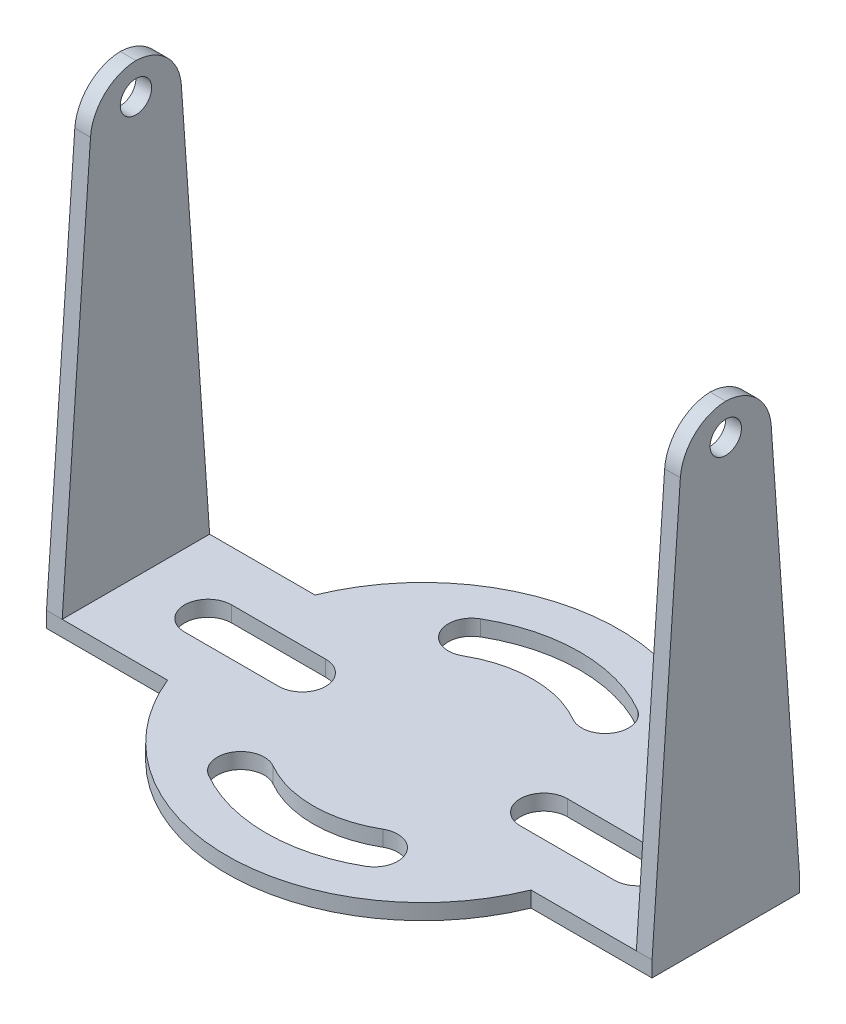
SolidWorks part; units mm, degrees
ref_plane "前视基准面" through (0, 0, 0) normal (0, 0, 1) x (1, 0, 0)
ref_plane "上视基准面" through (0, 0, 0) normal (0, 1, 0) x (1, 0, 0)
ref_plane "右视基准面" through (0, 0, 0) normal (1, 0, 0) x (0, 0, -1)
sketch "草图2" plane through (0, 0, 0) normal (0, 1, 0) x (1, 0, 0)
  line L1 (19.3, -4.7) -> (-19.3, -4.7)
  line L2 (19.3, -4.7) -> (19.3, 4.7)
  line L3 (19.3, 4.7) -> (-19.3, 4.7)
  line L4 (-19.3, -4.7) -> (-19.3, 4.7)
  line L5 (19.3, -4.7) -> (-19.3, 4.7) construction
  line L6 (19.3, 4.7) -> (-19.3, -4.7) construction
  point P0 (0, 0)
  dimension "D1" = 38.6
  dimension "D2" = 9.4
extrude "凸台-拉伸1" add sketch "草图2" along normal blind 1
sketch "草图3" plane through (0, 1, 0) normal (0, 1, 0) x (1, 0, 0)
  line L0 (-19.3, -4.7) -> (19.3, -4.7) construction
  line L1 (-19.3, 4.7) -> (-18.3, 4.7)
  line L2 (-19.3, 4.7) -> (-19.3, -4.7)
  line L3 (-19.3, -4.7) -> (-18.3, -4.7)
  line L4 (-18.3, 4.7) -> (-18.3, -4.7)
  line L5 (0, 0) -> (0, 4.7) construction
  line L6 (19.3, 4.7) -> (18.3, 4.7)
  line L7 (19.3, 4.7) -> (19.3, -4.7)
  line L8 (19.3, -4.7) -> (18.3, -4.7)
  line L9 (18.3, 4.7) -> (18.3, -4.7)
  line L10 (19.3, 4.7) -> (-19.3, 4.7) construction
  dimension "D1" = 1
extrude "凸台-拉伸2" add sketch "草图3" along normal blind 28.5
sketch "草图4" plane through (0, 1, 0) normal (0, 1, 0) x (1, 0, 0)
  line L0 (0, 0) -> (7, 0) construction
  line L4 (0, 0) -> (4.25, 7.3612)
  line L5 (0, 8.5) -> (0, 0) construction
  circle A0 centre (0, 0) radius 12.5
  circle A1 centre (0, 0) radius 7 construction
  arc A2 (-4.25, -7.3612) -> (4.25, -7.3612) centre (0, 0) ccw construction
  arc A3 (5, -8.6603) -> (-5, -8.6603) centre (0, 0) cw
  arc A4 (-4.25, 7.3612) -> (4.25, 7.3612) centre (0, 0) cw construction
  arc A5 (5, 8.6603) -> (-5, 8.6603) centre (0, 0) ccw
  arc A6 (3.5, 6.0622) -> (-3.5, 6.0622) centre (0, 0) ccw
  arc A7 (3.5, 6.0622) -> (5, 8.6603) centre (4.25, 7.3612) ccw
  arc A8 (-5, 8.6603) -> (-3.5, 6.0622) centre (-4.25, 7.3612) ccw
  arc A9 (3.5, -6.0622) -> (-3.5, -6.0622) centre (0, 0) cw
  arc A10 (3.5, -6.0622) -> (5, -8.6603) centre (4.25, -7.3612) cw
  arc A11 (-5, -8.6603) -> (-3.5, -6.0622) centre (-4.25, -7.3612) cw
  point P7 (0, -8.5)
  point P16 (0, 8.5)
  line M7 (-18.3, -4.7) -> (18.3, -4.7)
  line M9 (18.3, 4.7) -> (-18.3, 4.7)
  dimension "D1" = 25
  dimension "D2" = 14
  dimension "D6" = 3
  dimension "D7" = 30
extrude "凸台-拉伸3" add sketch "草图4" against normal blind 1 contours A8 A5 A7 A0 A6 M9 | A0 M7 M9 | A0 A3 A11 A9 A10 M7 region at (-4.4346, 1, -4.9444) region at (7.1481, 1, -4.4329) region at (0, 1, 4.9444)
sketch "草图5" plane through (0, 1, 0) normal (0, 1, 0) x (1, 0, 0)
  line L0 (13.7, 0) -> (7.7, 0) construction
  line L1 (13.7, -1.5) -> (7.7, -1.5)
  line L2 (13.7, 1.5) -> (7.7, 1.5)
  line L3 (0, 0) -> (0, -7) construction
  line L4 (-13.7, 0) -> (-7.7, 0) construction
  line L5 (-13.7, -1.5) -> (-7.7, -1.5)
  line L6 (-13.7, 1.5) -> (-7.7, 1.5)
  line L7 (19.3, -4.7) -> (19.3, 4.7) construction
  arc A0 (13.7, -1.5) -> (13.7, 1.5) centre (13.7, 0) ccw
  arc A1 (7.7, 1.5) -> (7.7, -1.5) centre (7.7, 0) ccw
  arc A2 (-3.5, -6.0622) -> (3.5, -6.0622) centre (0, 0) ccw construction
  arc A3 (-13.7, -1.5) -> (-13.7, 1.5) centre (-13.7, 0) cw
  arc A4 (-7.7, 1.5) -> (-7.7, -1.5) centre (-7.7, 0) cw
  point P3 (10.7, 0)
  point P15 (-10.7, 0)
  dimension "D1" = 3
  dimension "D2" = 5.6
  dimension "D3" = 6
extrude "切除-拉伸1" cut sketch "草图5" against normal through all
sketch "草图6" plane through (19.3, 0, 0) normal (1, 0, 0) x (0, 0, -1)
  line L0 (-4.7, 1) -> (-2.7, 29.5)
  line L1 (-4.7, 29.5) -> (4.7, 29.5) construction
  line L2 (-2.7, 29.5) -> (-4.7, 29.5)
  line L3 (-4.7, 29.5) -> (-4.7, 1)
  line L4 (-4.7, 1) -> (-4.5743, 0.6631)
  line L5 (0, 0) -> (0, 29.5) construction
  line L6 (4.7, 1) -> (4.5743, 0.6631)
  line L7 (4.7, 29.5) -> (4.7, 1)
  line L8 (2.7, 29.5) -> (4.7, 29.5)
  line L9 (4.7, 1) -> (2.7, 29.5)
  line M4 (4.7, 29.5) -> (-4.7, 29.5)
  line M5 (-4.7, 29.5) -> (-4.7, 0)
  dimension "D1" = 2
extrude "切除-拉伸2" cut sketch "草图6" against normal through all contours L0 M5 M4 | L9 L8 L7 region at (19.3, 20, 4.0333)
sketch "草图7" plane through (19.3, 0, 0) normal (1, 0, 0) x (0, 0, -1)
  line L0 (-2.7, 29.5) -> (2.7, 29.5) construction
  circle A0 centre (0, 27.5) radius 1
  point P5 (0, 29.5)
  dimension "D1" = 2
  dimension "D2" = 2
extrude "切除-拉伸3" cut sketch "草图7" against normal through all
fillet "圆角1" radius 3 4 edges at (-18.8, 29.5, -2.7) (-18.8, 29.5, 2.7) (18.8, 29.5, -2.7) (18.8, 29.5, 2.7)
